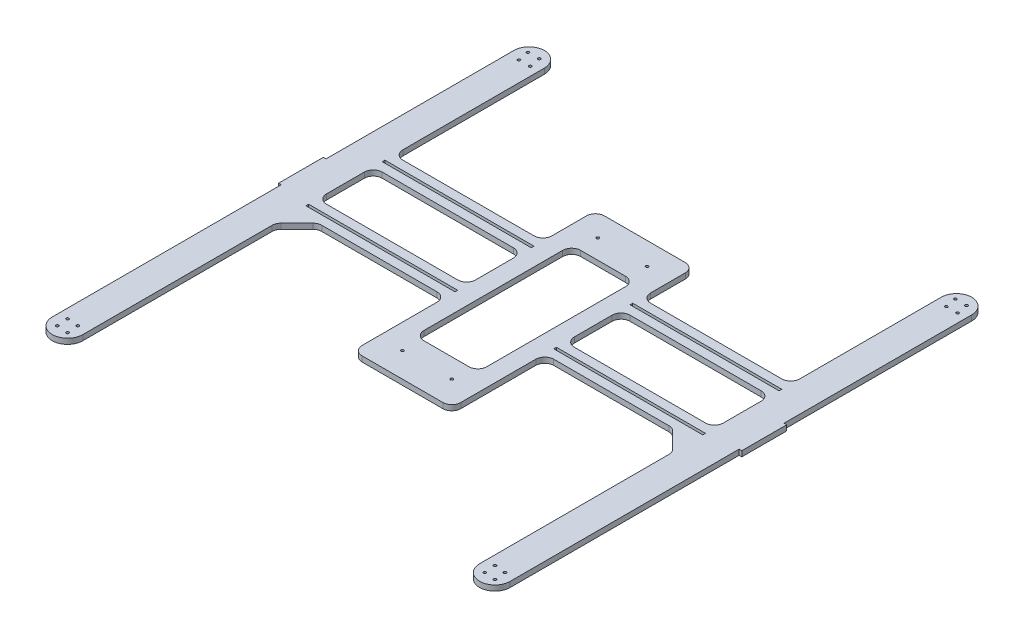
SolidWorks part; units mm, degrees
ref_plane "Front Plane" through (0, 0, 0) normal (0, 0, 1) x (1, 0, 0)
ref_plane "Top Plane" through (0, 0, 0) normal (0, 1, 0) x (1, 0, 0)
ref_plane "Right Plane" through (0, 0, 0) normal (1, 0, 0) x (0, 0, -1)
sketch "Sketch1" plane through (0, 0, 0) normal (0, 1, 0) x (1, 0, 0)
  line L1 (216, -40) -> (216, -255)
  line L4 (216, 78.5) -> (216, 81.5)
  line L5 (250, -255) -> (250, 0)
  line L6 (50, -120) -> (250, -120) construction
  line L7 (50, 150) -> (50, 91.5) construction
  line L8 (50, 150) -> (250, 120) construction
  line L10 (227.9078, 252.8902) -> (238.0922, 265.2304) construction
  line L11 (240.327, 253.0134) -> (225.673, 265.1073) construction
  line L12 (227.3431, -260.6569) -> (238.6569, -249.3431) construction
  line L13 (0, 25) -> (250, 25) construction
  line L14 (226.2825, -248.2825) -> (239.7175, -261.7175) construction
  line L18 (250, 0) -> (253, 0)
  line L19 (253, 0) -> (253, 50)
  line L20 (253, 50) -> (250, 50)
  line L21 (250, 50) -> (250, 259.0603)
  line L22 (50, 81.5) -> (50, 78.5) construction
  line L23 (50, 81.5) -> (50, 78.5)
  line L24 (50, -3.5) -> (50, -6.5) construction
  line L25 (50, -16.5) -> (50, -120) construction
  line L26 (50, 68.5) -> (50, 6.5)
  line L27 (-60, -5) -> (-226, -5) construction
  line L28 (216, 68.5) -> (216, 6.5)
  line L29 (-226, 68.5) -> (-226, 6.5)
  line L47 (-5, 150) -> (-5, -120) construction
  line L48 (-60, -120) -> (50, -120)
  line L53 (-60, 150) -> (50, 150)
  line L54 (50, 150) -> (50, 91.5)
  line L57 (250, -120) -> (250, -5) construction
  line L58 (50, -3.5) -> (50, -6.5)
  line L59 (216, -6.5) -> (50, -6.5)
  line L60 (50, 80) -> (216, 80) construction
  line L61 (250, 80) -> (250, 81.5) construction
  line L62 (216, 81.5) -> (50, 81.5)
  line L63 (216, -3.5) -> (50, -3.5)
  line L64 (250, 80) -> (250, 78.5) construction
  line L65 (216, 78.5) -> (50, 78.5)
  line L66 (-60, 80) -> (-226, 80) construction
  line L67 (50, 91.5) -> (216, 91.5)
  line L68 (-260, -120) -> (-260, -5) construction
  line L69 (50, 68.5) -> (216, 68.5)
  line L70 (50, -120) -> (50, -16.5)
  line L71 (-60, -16.5) -> (-60, -120) construction
  line L72 (50, -16.5) -> (192.5, -16.5)
  line L73 (-60, -3.5) -> (-60, -6.5) construction
  line L74 (50, 6.5) -> (216, 6.5)
  line L75 (192.5, -16.5) -> (216, -40)
  line L76 (50, -5) -> (216, -5) construction
  line L79 (216, -6.5) -> (216, -3.5)
  line L80 (216, 91.5) -> (216, 259.0603)
  line L81 (-60, 81.5) -> (-60, 78.5) construction
  line L83 (-10, 25) -> (-260, 25) construction
  line L84 (-237.3431, -260.6569) -> (-248.6569, -249.3431) construction
  line L85 (-248.6569, -260.6569) -> (-237.3431, -249.3431) construction
  line L87 (-60, 150) -> (-260, 120) construction
  line L88 (-60, 150) -> (-60, 91.5) construction
  line L89 (-60, -120) -> (-260, -120) construction
  line L90 (-226, 91.5) -> (-226, 259.0603)
  line L91 (-226, -6.5) -> (-226, -3.5)
  line L93 (-202.5, -16.5) -> (-226, -40)
  line L94 (-60, 6.5) -> (-226, 6.5)
  line L95 (-60, -16.5) -> (-202.5, -16.5)
  line L96 (-60, -120) -> (-60, -16.5)
  line L97 (-60, 68.5) -> (-226, 68.5)
  line L98 (-60, 91.5) -> (-226, 91.5)
  line L99 (-226, 78.5) -> (-60, 78.5)
  line L100 (-226, -3.5) -> (-60, -3.5)
  line L101 (-226, 81.5) -> (-60, 81.5)
  line L102 (-226, -6.5) -> (-60, -6.5)
  line L103 (-60, -3.5) -> (-60, -6.5)
  line L104 (-60, 150) -> (-60, 91.5)
  line L105 (-60, 68.5) -> (-60, 6.5)
  line L106 (-60, 81.5) -> (-60, 78.5)
  line L107 (-260, 50) -> (-260, 259.0603)
  line L108 (-263, 50) -> (-260, 50)
  line L109 (-263, 0) -> (-263, 50)
  line L110 (-260, 0) -> (-263, 0)
  line L111 (-260, -255) -> (-260, 0)
  line L112 (-226, 78.5) -> (-226, 81.5)
  line L113 (-226, -40) -> (-226, -255)
  line L116 (-235.673, 253.0134) -> (-250.327, 265.1073) construction
  line L119 (-248.0922, 252.8902) -> (-237.9078, 265.2304) construction
  line L121 (30, 103.5) -> (30, -71)
  line L122 (30, 103.5) -> (-40, 103.5)
  line L123 (-40, 103.5) -> (-40, -71)
  line L124 (-40, -71) -> (30, -71)
  arc A0 (216, -255) -> (250, -255) centre (233, -255) ccw
  arc A1 (216, 259.0603) -> (250, 259.0603) centre (233, 259.0603) cw
  circle A2 centre (233, -255) radius 135 construction
  circle A3 centre (233, 259.0603) radius 135 construction
  circle A4 centre (238.0922, 265.2304) radius 1.5
  circle A5 centre (225.673, 265.1073) radius 1.5
  circle A6 centre (227.9078, 252.8902) radius 1.5
  circle A7 centre (240.327, 253.0134) radius 1.5
  circle A8 centre (226.2825, -248.2825) radius 1.5
  circle A9 centre (238.6569, -249.3431) radius 1.5
  circle A10 centre (239.7175, -261.7175) radius 1.5
  circle A11 centre (227.3431, -260.6569) radius 1.5
  circle A33 centre (22.5, 125) radius 1.5
  circle A36 centre (-243, 259.0603) radius 135 construction
  circle A37 centre (-243, -255) radius 135 construction
  circle A39 centre (-32.5, 125) radius 1.5
  arc A48 (-226, 259.0603) -> (-260, 259.0603) centre (-243, 259.0603) ccw
  arc A49 (-226, -255) -> (-260, -255) centre (-243, -255) cw
  circle A50 centre (22.5, -92.5) radius 1.5
  circle A51 centre (-32.5, -92.5) radius 1.5
  circle A52 centre (-235.673, 253.0134) radius 1.5
  circle A53 centre (-237.9078, 265.2304) radius 1.5
  circle A54 centre (-248.0922, 252.8902) radius 1.5
  circle A55 centre (-250.327, 265.1073) radius 1.5
  circle A56 centre (-249.7175, -248.2825) radius 1.5
  circle A57 centre (-236.2825, -261.7175) radius 1.5
  circle A58 centre (-248.6569, -260.6569) radius 1.5
  circle A59 centre (-237.3431, -249.3431) radius 1.5
  point P12 (250, 120)
  point P13 (250, -120)
  point P15 (50, -120)
  point P134 (-60, -120)
  point P135 (-260, -120)
  point P136 (-260, 120)
  dimension "D1" = 17
  dimension "D3" = 270
  dimension "D4" = 270
  dimension "D12" = 3
  dimension "D13" = 3
  dimension "D14" = 3
  dimension "D15" = 3
  dimension "D20" = 3
  dimension "D21" = 3
  dimension "D22" = 3
  dimension "D23" = 3
  dimension "D7" = 16
  dimension "D11" = 3
  dimension "D5" = 240
  dimension "D6" = 200
  dimension "D8" = 19
  dimension "D9" = 16
  dimension "D10" = 19
  dimension "D16" = 270
  dimension "D17" = 45
  dimension "D18" = 16
  dimension "D19" = 19
extrude "Boss-Extrude1" add sketch "Sketch1" along normal blind 6 contours L1 A0 L5 L8 L4 L7 A11 A10 A9 A8 | L7 | A1 L4 L8 L5 A7 A6 A5 A4 region at (209.5727, 0, 22.9273)
fillet "Скругление1" radius 10 26 edges at (216, 3, -6.5) (216, 3, -68.5) (216, 3, -91.5) (-226, 3, -6.5) (-226, 3, -68.5) (-226, 3, -91.5) (-226, 3, 40) (-202.5, 3, 16.5) (216, 3, 40) (192.5, 3, 16.5) (-40, 3, 71) (30, 3, 71) (30, 3, -103.5) (-40, 3, -103.5) (-60, 3, -91.5) (-60, 3, -68.5) (-60, 3, 16.5) (-60, 3, -6.5) (50, 3, -68.5) (50, 3, -91.5) (50, 3, -6.5) (50, 3, 16.5) (-60, 3, -150) (50, 3, -150) (50, 3, 120) (-60, 3, 120)
